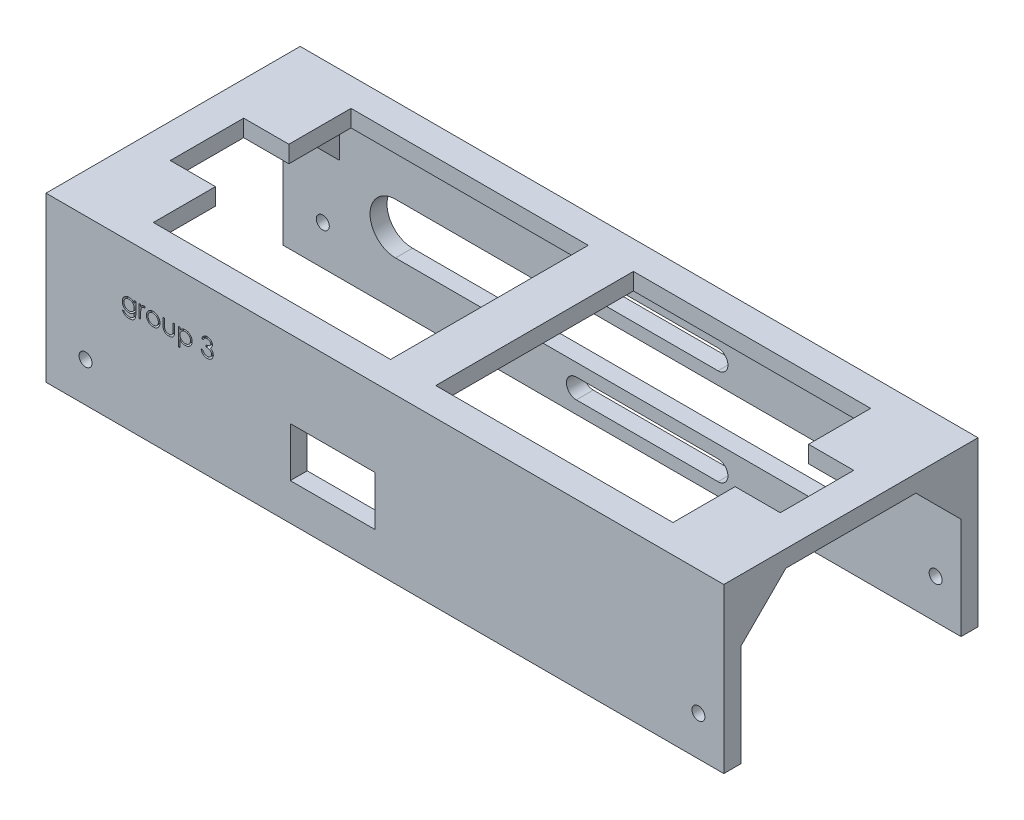
SolidWorks part; units mm, degrees
ref_plane "Front Plane" through (0, 0, 0) normal (0, 0, 1) x (1, 0, 0)
ref_plane "Top Plane" through (0, 0, 0) normal (0, 1, 0) x (1, 0, 0)
ref_plane "Right Plane" through (0, 0, 0) normal (1, 0, 0) x (0, 0, -1)
sketch "Sketch1" plane through (0, 0, 0) normal (0, 0, 1) x (1, 0, 0)
  line L9 (21.172, -17.9478) -> (91.172, -17.9478)
  line L10 (21.172, -17.9478) -> (21.172, -40.3878)
  line L11 (4, -8) -> (200.227, -8) construction
  line L12 (4, -8) -> (-67.5185, -8) construction
  line L13 (21.172, -40.3878) -> (91.172, -40.3878)
  line L14 (91.172, -17.9478) -> (91.172, -40.3878)
  line L15 (0, 0) -> (120, 0)
  line L16 (0, 0) -> (0, 29)
  line L17 (0, 29) -> (120, 29)
  line L18 (120, 0) -> (120, 29)
  circle A0 centre (4, 7) radius 1.15
  circle A1 centre (4, 7) radius 15 construction
  circle A3 centre (77.172, -29.1678) radius 3.6067
  circle A4 centre (116, 7) radius 15 construction
  circle A5 centre (116, 7) radius 1.15
  point P19 (21.172, -29.1678)
  dimension "D4" = 30
  dimension "D2" = 14
  dimension "D7" = 30
  dimension "D11" = 4
  dimension "D13" = 2.3
  dimension "D14" = 2.3
  dimension "D3" = 70
  dimension "D5" = 22.44
  dimension "D6" = 120
  dimension "D8" = 29
  dimension "D9" = 4
  dimension "D10" = 7
  dimension "D12" = 7
extrude "Boss-Extrude5" add sketch "Sketch1" along normal blind 45 contours L16 L15 L18 L17
shell "Shell9" thickness 3 removed face at (120, 14.5, 22.5) removed face at (60, 0, 22.5) removed face at (0, 14.5, 22.5)
sketch "Sketch3" plane through (0, 0, 0) normal (0, 0, -1) x (-1, 0, 0)
  line L0 (0, 0) -> (-120, 0) construction
  line L1 (-120, 0) -> (-120, 29) construction
  line L2 (0, 0) -> (0, 29) construction
  circle A0 centre (-7, 7) radius 1.15
  circle A1 centre (-115.5, 7) radius 1.15
  dimension "D1" = 2.3
  dimension "D2" = 2.3
  dimension "D3" = 7
  dimension "D4" = 4.5
  dimension "D5" = 7
  dimension "D6" = 7
extrude "Cut-Extrude2" cut sketch "Sketch3" against normal blind 79
sketch "Sketch6" plane through (0, 0, 0) normal (0, 0, -1) x (-1, 0, 0)
  line L0 (-76.9735, 21) -> (-51.8835, 21) construction
  line L1 (-76.9735, 22.75) -> (-51.8835, 22.75)
  line L2 (-76.9735, 19.25) -> (-51.8835, 19.25)
  line L7 (41.5249, -18.7743) -> (41.5249, -41.2143) construction
  line L8 (-94.8735, 12.5) -> (-19.8735, 12.5) construction
  line L9 (-94.8735, 17) -> (-19.8735, 17)
  line L10 (-94.8735, 8) -> (-19.8735, 8)
  line L11 (-19.8735, 12.5) -> (-17.326, 12.5) construction
  line L12 (-76.9735, 4) -> (-51.8835, 4) construction
  line L13 (-76.9735, 2.25) -> (-51.8835, 2.25)
  line L14 (-76.9735, 5.75) -> (-51.8835, 5.75)
  line L15 (4.7849, -29.9943) -> (74.7849, -29.9943) construction
  line L20 (4.7849, -18.7743) -> (74.7849, -18.7743)
  line L21 (4.7849, -18.7743) -> (4.7849, -41.2143)
  line L22 (4.7849, -41.2143) -> (74.7849, -41.2143)
  line L23 (74.7849, -18.7743) -> (74.7849, -41.2143)
  line L24 (-120, 0) -> (-120, 29) construction
  line L25 (63.3749, -18.7743) -> (63.3749, -41.2143) construction
  line L26 (0, 29) -> (-120, 29) construction
  arc A4 (-94.8735, 17) -> (-94.8735, 8) centre (-94.8735, 12.5) ccw
  arc A5 (-76.9735, 22.75) -> (-76.9735, 19.25) centre (-76.9735, 21) ccw
  arc A6 (-51.8835, 19.25) -> (-51.8835, 22.75) centre (-51.8835, 21) ccw
  arc A7 (-19.8735, 8) -> (-19.8735, 17) centre (-19.8735, 12.5) ccw
  arc A8 (-76.9735, 2.25) -> (-76.9735, 5.75) centre (-76.9735, 4) cw
  arc A9 (-51.8835, 5.75) -> (-51.8835, 2.25) centre (-51.8835, 4) cw
  circle A15 centre (16.1349, -29.9943) radius 1.5
  circle A16 centre (36.3249, -21.4943) radius 1.5
  circle A17 centre (36.3249, -38.4943) radius 1.5
  circle A18 centre (36.3249, -38.4943) radius 1.5
  circle A19 centre (27.0349, -29.9943) radius 2.3201
  point P11 (-64.4285, 21)
  point P19 (-57.3735, 12.5)
  point P31 (-64.4285, 4)
  dimension "D8" = 1.75
  dimension "D13" = 4.5
  dimension "D10" = 3
  dimension "D14" = 3
  dimension "D9" = 25.09
  dimension "D2" = 8.5
  dimension "D3" = 17.9
  dimension "D4" = 70
  dimension "D5" = 22.44
  dimension "D6" = 36.74
  dimension "D7" = 11.35
  dimension "D11" = 5.2
  dimension "D12" = 8.5
  dimension "D15" = 22.25
  dimension "D16" = 75
  dimension "D17" = 25.1265
  dimension "D18" = 11.41
  dimension "D19" = 16.5
extrude "Cut-Extrude8" cut sketch "Sketch6" against normal blind 23 contours L10 A7 L9 | L2 A6 L1 A5 | L13 A9 L14 A8 region at (64.4285, 21, 0) region at (57.3735, 12.5, 0)
sketch "Sketch7" plane through (0, 0, 45) normal (0, 0, 1) x (1, 0, 0)
  line L1 (43.2462, 15.2962) -> (58.2462, 15.2962)
  line L2 (43.2462, 15.2962) -> (43.2462, 6.5462)
  line L3 (43.2462, 6.5462) -> (58.2462, 6.5462)
  line L4 (58.2462, 15.2962) -> (58.2462, 6.5462)
  line L5 (0, 0) -> (120, 0) construction
  line L7 (0, 0) -> (0, 29) construction
  dimension "D1" = 43.2462
  dimension "D2" = 15
  dimension "D3" = 8.75
  dimension "D4" = 15.2962
extrude "Cut-Extrude9" cut sketch "Sketch7" against normal blind 20
sketch "Sketch13" plane through (0, 29, 0) normal (0, 1, 0) x (1, 0, 0)
  line L1 (0, 0) -> (120, 0) construction
  line L3 (64, -5) -> (114, -5)
  line L4 (6, -5) -> (56, -5)
  line L5 (6, -5) -> (6, -40)
  line L6 (6, -40) -> (56, -40)
  line L7 (56, -5) -> (56, -40)
  line L8 (0, -45) -> (0, 0) construction
  line L14 (64, -5) -> (64, -40)
  line L15 (64, -40) -> (114, -40)
  line L16 (114, -5) -> (114, -40)
  line L17 (120, -45) -> (120, 0) construction
  dimension "D1" = 6
  dimension "D2" = 5
  dimension "D3" = 50
  dimension "D4" = 50
  dimension "D5" = 6
  dimension "D6" = 35
  dimension "D7" = 35
  dimension "D8" = 5
extrude "Cut-Extrude14" cut sketch "Sketch13" against normal blind 10
sketch "Sketch17" plane through (0, 29, 0) normal (0, 1, 0) x (1, 0, 0)
  line L1 (6, -5) -> (14, -5)
  line L2 (6, -5) -> (6, -16)
  line L3 (6, -16) -> (14, -16)
  line L4 (14, -5) -> (14, -16)
  line L5 (6, -40) -> (14, -40)
  line L6 (6, -40) -> (6, -29)
  line L7 (6, -29) -> (14, -29)
  line L8 (14, -40) -> (14, -29)
  line L9 (114, -5) -> (106, -5)
  line L10 (114, -5) -> (114, -16)
  line L11 (114, -16) -> (106, -16)
  line L12 (106, -5) -> (106, -16)
  line L13 (114, -40) -> (106, -40)
  line L14 (114, -40) -> (114, -29)
  line L15 (114, -29) -> (106, -29)
  line L16 (106, -40) -> (106, -29)
  point P8 (14, -10.5)
  point P10 (14, -34.5)
  point P11 (10, -5)
  point P18 (10, -29)
  point P33 (106, -34.5)
  point P34 (110, -29)
  point P36 (110, -16)
  point P37 (106, -10.5)
  dimension "D1" = 11
  dimension "D2" = 8
  dimension "D4" = 11
  dimension "D5" = 8
  dimension "D7" = 11
  dimension "D8" = 8
  dimension "D9" = 11
  dimension "D10" = 8
extrude "Boss-Extrude6" add sketch "Sketch17" against normal blind 3
sketch "Sketch20" plane through (0, 0, 45) normal (0, 0, 1) x (1, 0, 0)
  line L0 (13.2558, 18.0126) -> (38.9246, 18.0126) construction
  text T0 "group 3"
extrude "Cut-Extrude15" cut sketch "Sketch20" against normal blind 1.5
sketch "Sketch21" plane through (0, 0, 0) normal (-1, 0, 0) x (0, 0, 1)
  line L0 (3, 26) -> (3, 18)
  line L1 (3, 0) -> (3, 26) construction
  line L2 (3, 18) -> (11, 26)
  line L3 (42, 26) -> (3, 26) construction
  line L4 (11, 26) -> (3, 26)
  line L5 (42, 26) -> (34, 26)
  line L6 (34, 26) -> (42, 18)
  line L7 (42, 0) -> (42, 26) construction
  line L8 (42, 18) -> (42, 26)
  dimension "D1" = 8
  dimension "D2" = 8
  dimension "D3" = 8
  dimension "D4" = 8
extrude "Boss-Extrude7" add sketch "Sketch21" against normal blind 10
sketch "Sketch22" plane through (120, 0, 0) normal (1, 0, 0) x (0, 0, -1)
  line L0 (-42, 26) -> (-42, 18)
  line L1 (-42, 18) -> (-34, 26)
  line L2 (-34, 26) -> (-42, 26)
  line L3 (-11, 26) -> (-3, 26)
  line L4 (-3, 26) -> (-3, 18)
  line L5 (-3, 18) -> (-11, 26)
extrude "Boss-Extrude8" add sketch "Sketch22" against normal blind 10
equation "\"slot­_width\"=25.09"
equation "\"D9@Sketch6\"=\"slot­_width\""
